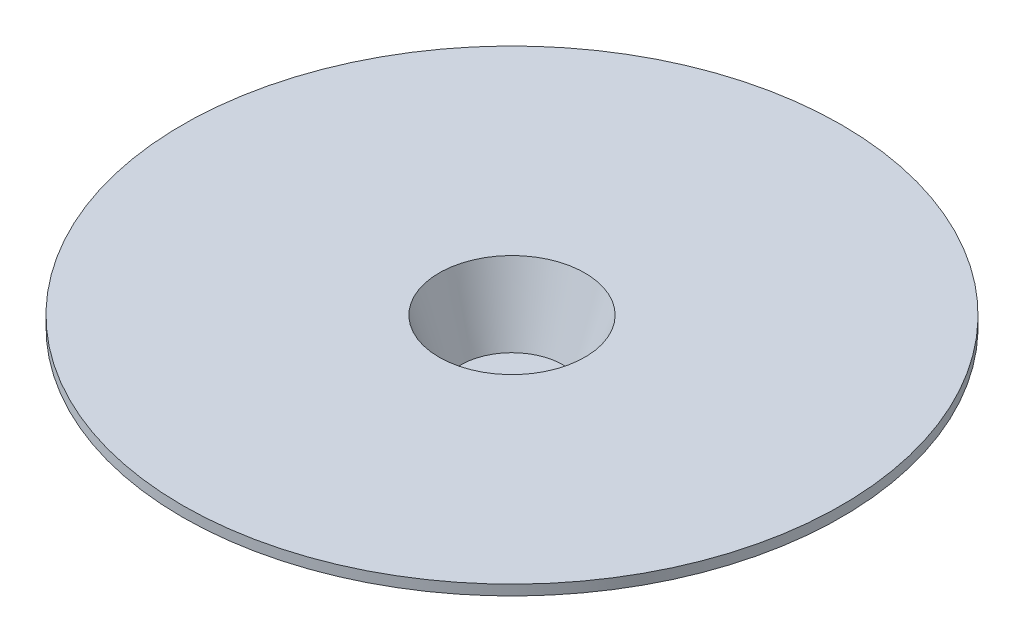
SolidWorks part; units mm, degrees
note: '?' marks a value the reader was unsure of.
material "ULTEM 9085"
ref_plane "Front Plane" through (0, 0, 0) normal (0, 0, 1) x (1, 0, 0)
ref_plane "Top Plane" through (0, 0, 0) normal (0, 1, 0) x (1, 0, 0)
ref_plane "Right Plane" through (0, 0, 0) normal (1, 0, 0) x (0, 0, -1)
other "Center of Mass"
sketch "Sketch1" plane through (0, 0, 0) normal (0, 0, 1) x (1, 0, 0)
  line L0 (0, -40.25) -> (0, -46.25)
  line L1 (0, -40.25) -> (30, -40.25)
  line L2 (30, -40.25) -> (42.6498, 0)
  line L3 (42.6498, 0) -> (192.6498, 0)
  line L4 (94.9574, 0) -> (-94.9574, 0) construction
  line L5 (192.6498, 0) -> (192.6498, -6)
  line L6 (42.6498, 0) -> (42.6498, -31.4331) construction
  line L7 (192.6498, -6) -> (46.8968, -6)
  line L8 (36.1179, -40.2971) -> (46.8968, -6)
  line L9 (36.1179, -40.2971) -> (55.5, -40.2971)
  line L10 (55.5, -40.2971) -> (55.5, -46.25)
  line L11 (55.5, -46.25) -> (0, -46.25)
  line L12 (0, -25.4375) -> (0, 25.4375) construction
  point P15 (0, -43.25)
  point P16 (55.5, -43.2736)
  point P24 (36.3249, -20.125)
  point P25 (41.5074, -23.1486)
  dimension "D1" = 72.553
  dimension "D2" = 30
  dimension "D3" = 150
  dimension "D4" = 6
  dimension "D5" = 6
  dimension "D6" = 55.5
  dimension "D7" = 34.2971
  dimension "D8" = 40.25
  dimension "D9" = 6
revolve "Revolve2" add sketch "Sketch1" angle 360 about L0
ref_axis "Axis1" through (0, 0, 0) along (0, -1, 0)?
